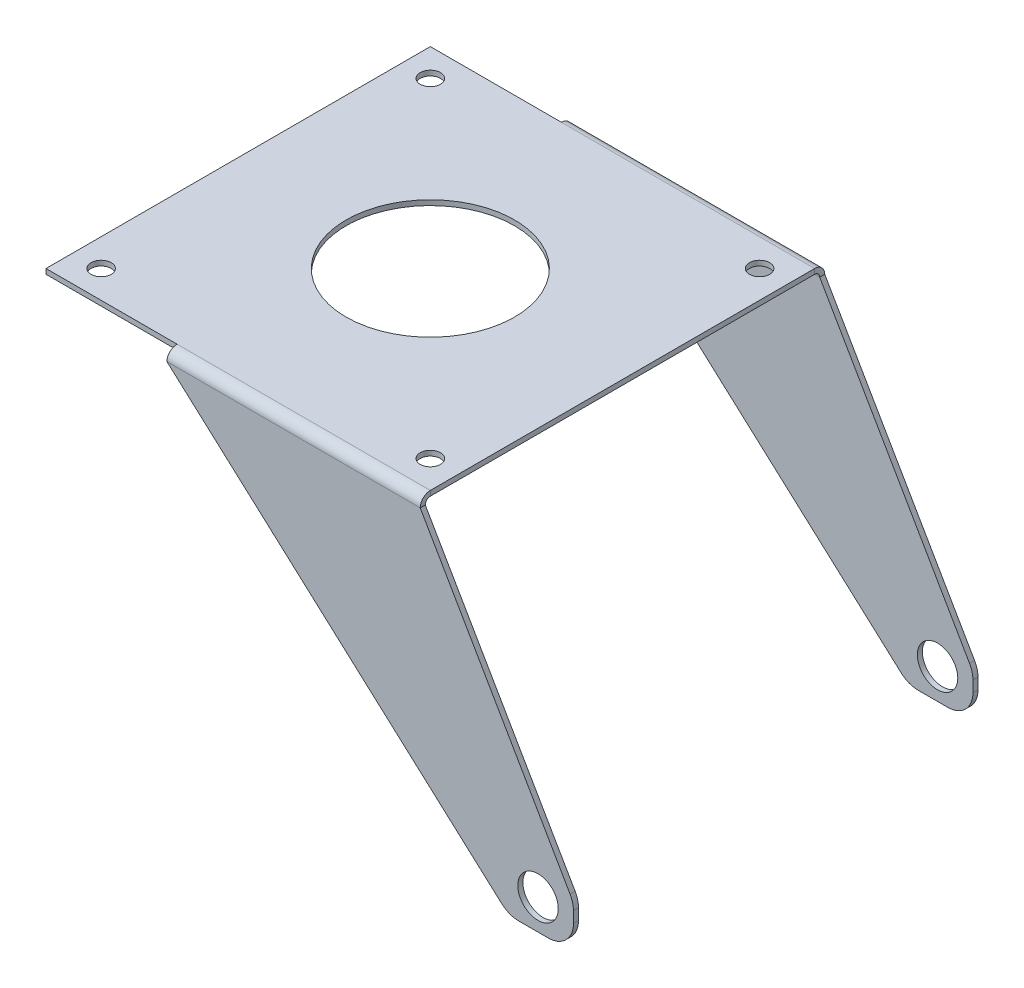
SolidWorks part; units mm, degrees
note: '?' marks a value the reader was unsure of. The reader was unsure of these and kept them because the rebuilt part matched: flange length of "Edge-Flange1".
ref_plane "Front Plane" through (0, 0, 0) normal (0, 0, 1) x (1, 0, 0)
ref_plane "Top Plane" through (0, 0, 0) normal (0, 1, 0) x (1, 0, 0)
ref_plane "Right Plane" through (0, 0, 0) normal (1, 0, 0) x (0, 0, -1)
sketch "Sketch2" plane through (0, 0, 0) normal (0, 1, 0) x (1, 0, 0)
  line L1 (-38, -38) -> (38, -38)
  line L2 (-38, -38) -> (-38, 38)
  line L3 (-38, 38) -> (38, 38)
  line L4 (38, -38) -> (38, 38)
  line L5 (-38, -38) -> (38, 38) construction
  line L6 (-38, 38) -> (38, -38) construction
  point P0 (0, 0)
  dimension "D1" = 76
  dimension "D2" = 76
base flange "Base-Flange1" sketch "Sketch2" thickness 1 reverse thickness direction no parameters "D1"=0.6
ref_axis "Axis1" through (0, -23.1417, 0) along (0, 1, 0)?
sketch "Sketch7" plane through (0, 0, 0) normal (0, 1, 0) x (1, 0, 0)
  line L1 (-38, -38) -> (38, -38)
  line L2 (-38, -38) -> (-38, 38)
  line L3 (-38, 38) -> (38, 38)
  line L4 (38, -38) -> (38, 38)
  line L5 (-38, -38) -> (38, 38) construction
  line L6 (-38, 38) -> (38, -38) construction
  circle A0 centre (32.55, 32.55) radius 2
  circle A1 centre (0, 0) radius 16.65
  point P0 (0, 0)
  dimension "D1" = 4
  dimension "D3" = 33.3
  dimension "D2" = 5.45
extrude "Cut-Extrude2" cut sketch "Sketch7" against normal blind 10 contours A0 | A1 normal cut yes
pattern_circular "CirPattern1" count 4 over 360 about axis through (0, 0, 0) along (0, 1, 0) of "Cut-Extrude2"
edge flange "Edge-Flange1" sketch "Sketch10" flange angle 90 flange length 62 flange position bend outside bend radius 1 thickness 1 relief rectangular parameters "D6"=10
sketch "Sketch10" plane through (0, -1, -38) normal (0, 0, -1) x (1, 0, 0)
  line L0 (38, 0) -> (-38, 0) construction
  line L1 (38, 0) -> (-12.0838, 0)
  line L2 (-12.0838, 0) -> (-12.0838, 62)
  line L3 (-12.0838, 62) -> (38, 62)
  line L4 (38, 62) -> (38, 0)
  dimension "D1" = 62
bend "EdgeBend1" bend radius 1 bend angle 90 parameters "D5"=1
sketch "Sketch14" plane through (0, 0, -40) normal (0, 0, -1) x (-1, 0, 0)
  line L0 (-38, -63) -> (12.0838, -63) construction
  line L1 (-38, -2) -> (-68.3, -2)
  line L2 (-38, -2) -> (-38, -63)
  line L3 (-38, -63) -> (-68.3, -63)
  line L4 (-68.3, -2) -> (-68.3, -63)
  dimension "D1" = 30.3
base flange "Tab1" sketch "Sketch14" thickness 1 reverse thickness direction no parameters "D1"=0.6
sketch "Sketch19" plane through (0, 0, -40) normal (0, 0, -1) x (-1, 0, 0)
  line L0 (-38, -2) -> (-68.3, -2) construction
  line L2 (-68.3, -2) -> (-68.3, -63) construction
  circle A0 centre (-61.3, -57) radius 4
  dimension "D2" = 8
  dimension "D3" = 7
  dimension "D1" = 55
fillet "Fillet1" radius 5 1 edges at (68.3, -63, -39.5)
sketch "Sketch20" plane through (0, 0, -40) normal (0, 0, -1) x (-1, 0, 0)
  line L0 (-38, -2) -> (-68.3, -54.4826)
  line L1 (-68.3, -2) -> (-68.3, -58) construction
  line L2 (-68.3, -54.4826) -> (-68.3, -2)
  line L3 (-68.3, -2) -> (-38, -2)
extrude "Cut-Extrude4" cut sketch "Sketch20" against normal blind 10 normal cut yes
sketch "Sketch21" plane through (0, 0, -40) normal (0, 0, -1) x (-1, 0, 0)
  line L0 (12.0838, -2) -> (-55.545, -63)
  line L1 (-63.3, -63) -> (12.0838, -63) construction
  line L2 (-55.545, -63) -> (12.0838, -63)
  line L3 (12.0838, -63) -> (12.0838, -2)
extrude "Cut-Extrude5" cut sketch "Sketch21" against normal blind 10 normal cut yes
fillet "Fillet2" radius 5 2 edges at (55.545, -63, -39.5) (68.3, -54.4826, -39.5)
extrude "Cut-Extrude6" cut sketch "Sketch19" against normal blind 10 contours A0 normal cut yes
mirror "Mirror1" about plane through (0, 0, 0) normal (0, 0, 1) of "Cut-Extrude6", "Cut-Extrude4", "Tab1", "Fillet2", "Cut-Extrude5", "Fillet1", "Edge-Flange1"
bend "MirrorBend1" bend radius 1 bend angle 90 parameters "D5"=2
sketch "Bend-Lines1" [suppressed] plane through (0, 0, 0) normal (0, 1, 0) x (1, 0, 0)
sketch "Bounding-Box1" [suppressed] plane through (0, 0, 0) normal (0, 1, 0) x (1, 0, 0)
sketch "Sketch22" [suppressed] plane through (0, 0, 0) normal (0, 1, 0) x (1, 0, 0)
  line L0 (-6, -39.1781) -> (6, -39.1781) construction
  line L1 (-12.0838, -39.1781) -> (38, -39.1781) construction
  line L2 (-6, -38.4281) -> (6, -38.4281)
  line L3 (-6, -39.9281) -> (6, -39.9281)
  line L7 (19.7907, -39.1781) -> (31.7907, -39.1781) construction
  line L8 (19.7907, -38.4281) -> (31.7907, -38.4281)
  line L9 (19.7907, -39.9281) -> (31.7907, -39.9281)
  arc A0 (-6, -38.4281) -> (-6, -39.9281) centre (-6, -39.1781) ccw
  arc A1 (6, -39.9281) -> (6, -38.4281) centre (6, -39.1781) ccw
  arc A4 (19.7907, -38.4281) -> (19.7907, -39.9281) centre (19.7907, -39.1781) ccw
  arc A5 (31.7907, -39.9281) -> (31.7907, -38.4281) centre (31.7907, -39.1781) ccw
  point P4 (0, -39.1781)
  point P17 (25.7907, -39.1781)
  dimension "D1" = 1.5
  dimension "D2" = 12
  dimension "D5" = 1.5
  dimension "D6" = 12
extrude "Cut-Extrude7" [suppressed] cut sketch "Sketch22" against normal blind 10
mirror "Mirror2" [suppressed] about plane through (0, 0, 0) normal (0, 0, 1)
fillet "Fillet3" [suppressed] radius 5
fillet "Fillet4" [suppressed] radius 10
fillet "Fillet5" [suppressed] radius 3
fillet "Fillet6" [suppressed] radius 3
fillet "Fillet7" [suppressed] radius 3
sheet metal parameters "Sheet-Metal(1)" thickness 1 parameters "D1"=0.6
flat pattern "Flat-Pattern(1)" [suppressed]
sketch "Bend-Lines2" plane through (0, 0, 0) normal (0, 1, 0) x (1, 0, 0)
sketch "Bounding-Box2" [suppressed] plane through (0, 0, 0) normal (0, 1, 0) x (1, 0, 0)
sheet metal parameters "Sheet-Metal(3)" thickness 1 parameters "D1"=0.6
flat pattern "Flat-Pattern(1)"
sketch "Bend-Lines2" plane through (0, 0, 0) normal (0, 1, 0) x (1, 0, 0)
sketch "Bounding-Box2" [suppressed] plane through (0, 0, 0) normal (0, 1, 0) x (1, 0, 0)
sheet metal parameters "Sheet-Metal(4)" thickness 1 parameters "D1"=0.6
flat pattern "Flat-Pattern(1)"
sketch "Bend-Lines2" plane through (0, 0, 0) normal (0, 1, 0) x (1, 0, 0)
sketch "Bounding-Box2" [suppressed] plane through (0, 0, 0) normal (0, 1, 0) x (1, 0, 0)
sheet metal parameters "Sheet-Metal(5)" thickness 1 parameters "D1"=0.6
flat pattern "Flat-Pattern(1)" [suppressed]
sketch "Bend-Lines2" plane through (0, 0, 0) normal (0, 1, 0) x (1, 0, 0)
sketch "Bounding-Box2" [suppressed] plane through (0, 0, 0) normal (0, 1, 0) x (1, 0, 0)
bend of the flat pattern "Flatten-<EdgeBend1>1"
sheet metal parameters "Sheet-Metal(6)" thickness 1 parameters "D1"=0.6
flat pattern "Flat-Pattern(6)" [suppressed]
sketch "Bend-Lines3" plane through (0, 0, 0) normal (0, 1, 0) x (1, 0, 0)
sketch "Bounding-Box3" [suppressed] plane through (0, 0, 0) normal (0, 1, 0) x (1, 0, 0)
bend of the flat pattern "Flatten-<EdgeBend1>2"
sheet metal parameters "Sheet-Metal(8)" thickness 1 parameters "D1"=0.6
flat pattern "Flat-Pattern(6)" [suppressed]
sketch "Bend-Lines3" plane through (0, 0, 0) normal (0, 1, 0) x (1, 0, 0)
sketch "Bounding-Box3" [suppressed] plane through (0, 0, 0) normal (0, 1, 0) x (1, 0, 0)
bend of the flat pattern "Flatten-<EdgeBend1>2"
sheet metal parameters "Sheet-Metal(9)" thickness 1 parameters "D1"=0.6
flat pattern "Flat-Pattern(6)" [suppressed]
sketch "Bend-Lines3" plane through (0, 0, 0) normal (0, 1, 0) x (1, 0, 0)
sketch "Bounding-Box3" [suppressed] plane through (0, 0, 0) normal (0, 1, 0) x (1, 0, 0)
bend of the flat pattern "Flatten-<EdgeBend1>2"
sheet metal parameters "Sheet-Metal(10)" thickness 1 parameters "D1"=0.6
flat pattern "Flat-Pattern(6)"
sketch "Bend-Lines3" plane through (0, 0, 0) normal (0, 1, 0) x (1, 0, 0)
  line L0 (-12.0838, -39.1781) -> (38, -39.1781) construction
  line L1 (38, 39.1781) -> (-12.0838, 39.1781) construction
  line L2 (-12.0838, -39.1781) -> (38, -39.1781) construction
  line L3 (38, 39.1781) -> (-12.0838, 39.1781) construction
sketch3d "Bounding-Box3" [suppressed]
  line L0 (-38, -101.3562, 0) -> (-38, 101.3562, 0) construction
  line L1 (68.3, -101.3562, 0) -> (68.3, 101.3562, 0) construction
  line L2 (-38, -101.3562, 0) -> (68.3, -101.3562, 0) construction
  line L3 (-38, 101.3562, 0) -> (68.3, 101.3562, 0) construction
bend of the flat pattern "Flatten-<EdgeBend1>2"
bend of the flat pattern "Flatten-<MirrorBend1>1"
sheet metal parameters "Sheet-Metal(11)" thickness 1 parameters "D1"=0.6
flat pattern "Flat-Pattern(6)" [suppressed]
sketch "Bend-Lines3" plane through (0, 0, 0) normal (0, 1, 0) x (1, 0, 0)
sketch "Bounding-Box3" [suppressed] plane through (0, 0, 0) normal (0, 1, 0) x (1, 0, 0)
bend of the flat pattern "Flatten-<EdgeBend1>2"
